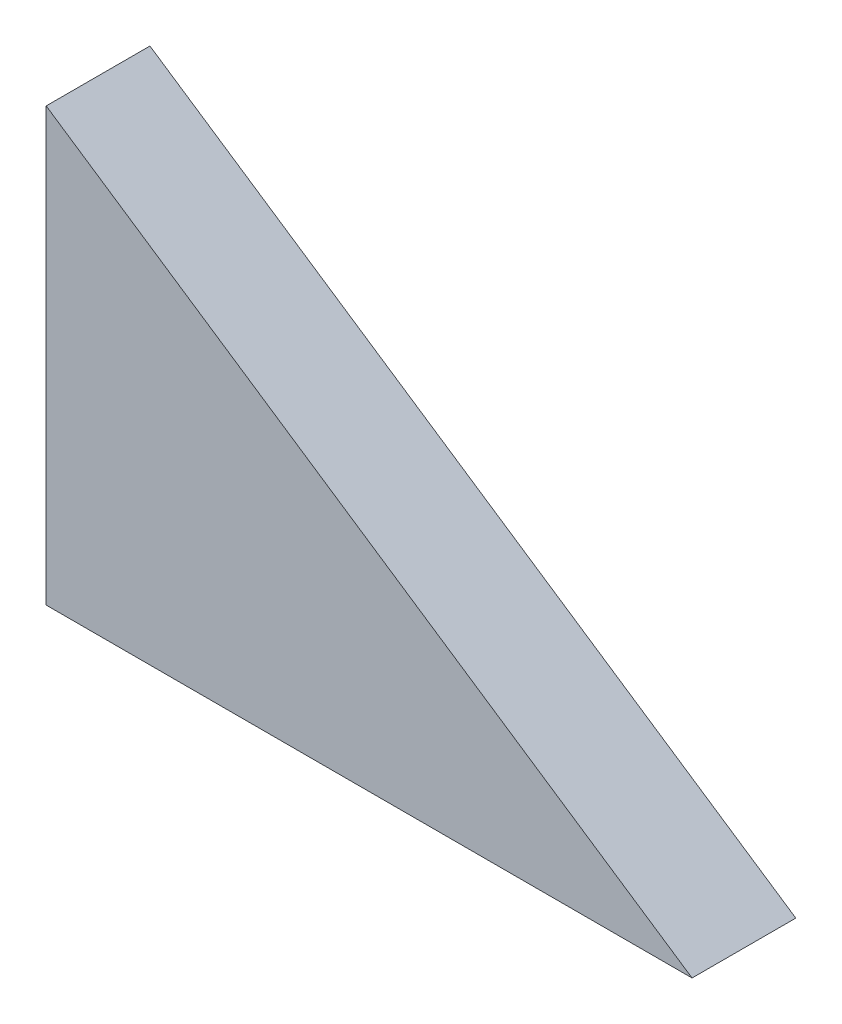
SolidWorks part; units mm, degrees
material "Клен"
ref_plane "Спереди" through (0, 0, 0) normal (0, 0, 1) x (1, 0, 0)
ref_plane "Сверху" through (0, 0, 0) normal (0, 1, 0) x (1, 0, 0)
ref_plane "Справа" through (0, 0, 0) normal (1, 0, 0) x (0, 0, -1)
sketch "Эскиз1" plane through (0, 0, 0) normal (0, 0, 1) x (1, 0, 0)
  line L0 (6, 6.0784) -> (6, 31.0784)
  line L1 (6, 31.0784) -> (43.35, 6.0784)
  line L3 (43.35, 6.0784) -> (6, 6.0784)
extrude "Бобышка-Вытянуть1" add sketch "Эскиз1" against normal blind 6
